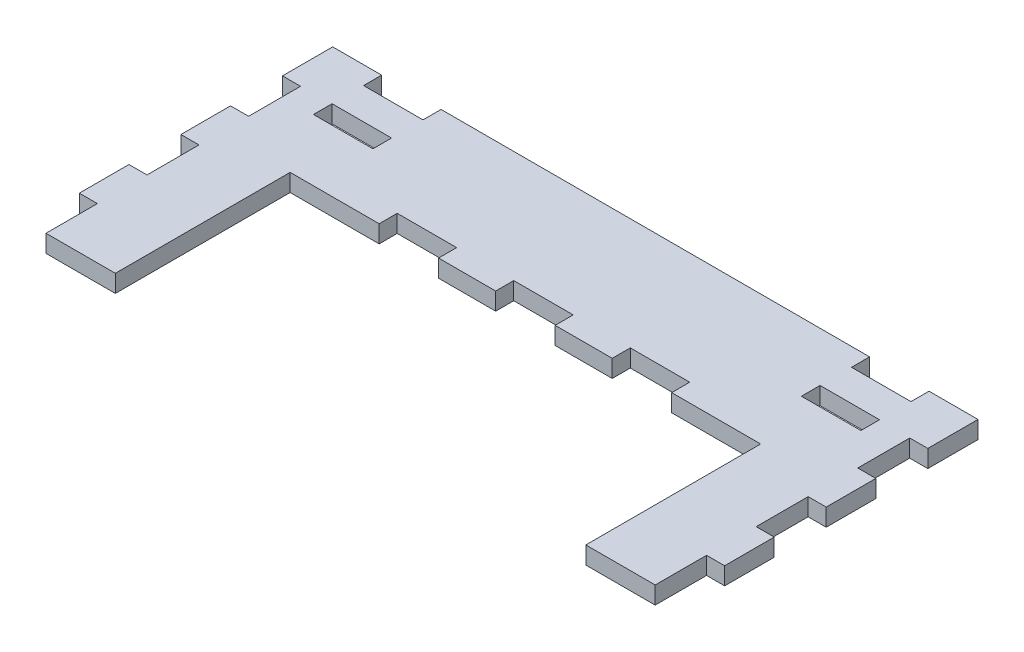
SolidWorks part; units mm, degrees
ref_plane "Front Plane" through (0, 0, 0) normal (0, 0, 1) x (1, 0, 0)
ref_plane "Top Plane" through (0, 0, 0) normal (0, 1, 0) x (1, 0, 0)
ref_plane "Right Plane" through (0, 0, 0) normal (1, 0, 0) x (0, 0, -1)
sketch "Sketch1" plane through (0, 0, 0) normal (0, 1, 0) x (1, 0, 0)
  line L0 (0, 0) -> (0, 52.3) construction
  line L1 (-55.3722, 52.3) -> (55.3722, 52.3)
  line L2 (-55.3722, 52.3) -> (-55.3722, 0)
  line L3 (-55.3722, 0) -> (55.3722, 0) construction
  line L4 (55.3722, 52.3) -> (55.3722, 0)
  line L6 (40.3722, 0) -> (40.3722, 30)
  line L7 (40.3722, 30) -> (-40.3722, 30)
  line L8 (-40.3722, 30) -> (-40.3722, 0)
  line L9 (55.3722, 0) -> (40.3722, 0)
  line L10 (-40.3722, 0) -> (-55.3722, 0)
  dimension "D1" = 15
sketch "Sketch2" plane through (0, 0, 0) normal (1, 0, 0) x (0, 0, -1)
  line L1 (0, 0) -> (52.3, 0)
  line L2 (0, 0) -> (0, 3)
  line L3 (0, 3) -> (52.3, 3)
  line L4 (52.3, 0) -> (52.3, 3)
extrude "Boss-Extrude1" add sketch "Sketch1" along normal up to vertex (3 mm away) up to point (0, 3, -52.3)
sketch "Sketch3" plane through (0, 0, 0) normal (0, 1, 0) x (1, 0, 0)
  line L0 (55.3722, 52.3) -> (55.3722, 0) construction
  line L1 (55.3722, 0) -> (40.3722, 0) construction
  line L2 (40.3722, 0) -> (40.3722, 30) construction
  line L3 (40.3722, 30) -> (-40.3722, 30) construction
  line L4 (-40.3722, 30) -> (-40.3722, 0) construction
  line L5 (-40.3722, 0) -> (-55.3722, 0) construction
  line L6 (-55.3722, 52.3) -> (-55.3722, 0) construction
  line L7 (-55.3722, 52.3) -> (55.3722, 52.3) construction
  line L8 (55.3722, 52.3) -> (55.3722, 0) construction
  line L9 (55.3722, 0) -> (40.3722, 0) construction
  line L10 (40.3722, 0) -> (40.3722, 30) construction
  line L11 (40.3722, 30) -> (-40.3722, 30) construction
  line L12 (-40.3722, 30) -> (-40.3722, 0) construction
  line L13 (-40.3722, 0) -> (-55.3722, 0) construction
  line L14 (-55.3722, 52.3) -> (-55.3722, 0) construction
  line L15 (-55.3722, 52.3) -> (55.3722, 52.3) construction
  line L16 (36.8722, 52.3) -> (36.8722, 30) construction
  line L17 (-36.8722, 52.3) -> (-36.8722, 30) construction
  line L18 (55.3722, 49.3) -> (-55.3722, 49.3) construction
  line L19 (55.3722, 40.7) -> (-55.3722, 40.7) construction
  line L20 (55.3722, 43.7) -> (-55.3722, 43.7) construction
  line L21 (-55.3722, 33) -> (55.3722, 33) construction
  line L22 (52.3722, 52.3) -> (52.3722, 0) construction
  line L23 (-52.3722, 52.3) -> (-52.3722, 0) construction
  line L24 (0, 52.3) -> (0, 0) construction
  line L25 (46.8722, 52.3) -> (46.8722, 49.3) construction
  line L26 (46.8722, 43.7) -> (46.8722, 40.7) construction
  line L27 (40.3722, 30) -> (55.3722, 30) construction
  line L28 (-40.3722, 30) -> (-55.3722, 30) construction
  line L30 (35, 33) -> (35, 30) construction
  line L33 (25, 33) -> (25, 30) construction
  line L34 (25, 31.5) -> (35, 31.5) construction
  line L35 (5, 33) -> (5, 30) construction
  line L36 (5, 31.5) -> (-5, 31.5) construction
  line L37 (25, 31.5) -> (15, 31.5) construction
  line L38 (15, 31.5) -> (5, 31.5) construction
  line L39 (15, 33) -> (15, 30) construction
  line L43 (52.3722, 43.5833) -> (55.3722, 43.5833) construction
  line L44 (55.3722, 34.8667) -> (52.3722, 34.8667) construction
  line L45 (53.8722, 34.8667) -> (53.8722, 43.5833) construction
  line L46 (53.8722, 43.5833) -> (53.8722, 52.3) construction
  line L47 (53.8722, 34.8667) -> (53.8722, 26.15) construction
  line L48 (55.3722, 26.15) -> (52.3722, 26.15) construction
  line L49 (55.3722, 17.4333) -> (52.3722, 17.4333) construction
  line L50 (53.8722, 26.15) -> (53.8722, 17.4333) construction
  line L51 (55.3722, 8.7167) -> (52.3722, 8.7167) construction
  line L52 (53.8722, 17.4333) -> (53.8722, 8.7167) construction
  line L53 (53.8722, 8.7167) -> (53.8722, 0) construction
  dimension "D1" = 10
  dimension "D2" = 8.7167
  dimension "D3" = 10
sketch "Sketch4" plane through (0, 0, 0) normal (0, 1, 0) x (1, 0, 0)
  line L0 (0, 0) -> (0, 52.3) construction
  line L1 (46.9722, 52.4) -> (36.7722, 52.4)
  line L2 (46.9722, 52.4) -> (46.9722, 49.2)
  line L3 (46.9722, 49.2) -> (36.7722, 49.2)
  line L4 (36.7722, 52.4) -> (36.7722, 49.2)
  line L5 (46.9722, 43.8) -> (36.7722, 43.8)
  line L6 (46.9722, 43.8) -> (46.9722, 40.6)
  line L7 (46.9722, 40.6) -> (36.7722, 40.6)
  line L8 (36.7722, 43.8) -> (36.7722, 40.6)
  line L9 (55.4722, 43.6833) -> (52.2722, 43.6833)
  line L10 (55.4722, 43.6833) -> (55.4722, 34.7667)
  line L11 (55.4722, 34.7667) -> (52.2722, 34.7667)
  line L12 (52.2722, 43.6833) -> (52.2722, 34.7667)
  line L13 (55.4722, 26.25) -> (52.2722, 26.25)
  line L14 (55.4722, 26.25) -> (55.4722, 17.3333)
  line L15 (55.4722, 17.3333) -> (52.2722, 17.3333)
  line L16 (52.2722, 26.25) -> (52.2722, 17.3333)
  line L17 (55.4722, 8.8167) -> (52.2722, 8.8167)
  line L18 (55.4722, 8.8167) -> (55.4722, -0.1)
  line L19 (55.4722, -0.1) -> (52.2722, -0.1)
  line L20 (52.2722, 8.8167) -> (52.2722, -0.1)
  line L21 (20, 33.1) -> (20, 33) construction
  line L22 (20, 29.9) -> (20, 30) construction
  line L23 (40.3722, 30) -> (-40.3722, 30) construction
  line L24 (-55.3722, 33) -> (55.3722, 33) construction
  line L25 (25.1, 33.1) -> (14.9, 33.1)
  line L26 (25.1, 33.1) -> (25.1, 29.9)
  line L27 (25.1, 29.9) -> (14.9, 29.9)
  line L28 (14.9, 33.1) -> (14.9, 29.9)
  line L29 (5.1, 33.1) -> (-5.1, 33.1)
  line L30 (5.1, 33.1) -> (5.1, 29.9)
  line L31 (5.1, 29.9) -> (-5.1, 29.9)
  line L32 (-5.1, 33.1) -> (-5.1, 29.9)
  line L33 (0, 0) -> (0, 52.3) construction
  line L34 (41.8722, 52.4) -> (41.8722, 52.3) construction
  line L35 (41.8722, 49.2) -> (41.8722, 49.3) construction
  line L36 (36.7722, 50.8) -> (36.8722, 50.8) construction
  line L37 (46.9722, 50.8) -> (46.8722, 50.8) construction
  line L38 (46.8722, 52.3) -> (46.8722, 49.3) construction
  line L39 (-55.3722, 52.3) -> (55.3722, 52.3) construction
  line L40 (55.3722, 49.3) -> (-55.3722, 49.3) construction
  line L41 (36.8722, 52.3) -> (36.8722, 30) construction
  line L42 (52.2722, 39.225) -> (52.3722, 39.225) construction
  line L43 (55.4722, 39.225) -> (55.3722, 39.225) construction
  line L44 (53.8722, 43.6833) -> (53.8722, 43.5833) construction
  line L45 (53.8722, 34.7667) -> (53.8722, 34.8667) construction
  line L46 (53.8722, 26.25) -> (53.8722, 26.15) construction
  line L47 (53.8722, 17.3333) -> (53.8722, 17.4333) construction
  line L48 (53.8722, 8.8167) -> (53.8722, 8.7167) construction
  line L49 (53.8722, -0.1) -> (53.8722, 0) construction
  line L50 (41.8722, 43.8) -> (41.8722, 43.7) construction
  line L51 (41.8722, 40.6) -> (41.8722, 40.7) construction
  line L52 (55.3722, 43.7) -> (-55.3722, 43.7) construction
  line L53 (55.3722, 40.7) -> (-55.3722, 40.7) construction
  line L54 (52.3722, 43.5833) -> (55.3722, 43.5833) construction
  line L55 (55.3722, 34.8667) -> (52.3722, 34.8667) construction
  line L56 (52.3722, 52.3) -> (52.3722, 0) construction
  line L57 (55.3722, 52.3) -> (55.3722, 0) construction
  line L58 (55.3722, 26.15) -> (52.3722, 26.15) construction
  line L59 (55.3722, 17.4333) -> (52.3722, 17.4333) construction
  line L60 (55.3722, 0) -> (40.3722, 0) construction
  line L61 (55.3722, 8.7167) -> (52.3722, 8.7167) construction
  line L70 (25.1, 31.5) -> (25, 31.5) construction
  line L71 (14.9, 31.5) -> (15, 31.5) construction
  line L72 (5.1, 31.5) -> (5, 31.5) construction
  line L73 (5, 33) -> (5, 30) construction
  line L74 (15, 33) -> (15, 30) construction
  line L75 (25, 33) -> (25, 30) construction
  line L76 (-55.4722, 8.8167) -> (-52.2722, 8.8167)
  line L77 (-55.4722, 8.8167) -> (-55.4722, -0.1)
  line L78 (-55.4722, -0.1) -> (-52.2722, -0.1)
  line L79 (-52.2722, 8.8167) -> (-52.2722, -0.1)
  line L80 (-55.4722, 26.25) -> (-52.2722, 26.25)
  line L81 (-55.4722, 26.25) -> (-55.4722, 17.3333)
  line L82 (-55.4722, 17.3333) -> (-52.2722, 17.3333)
  line L83 (-52.2722, 26.25) -> (-52.2722, 17.3333)
  line L84 (-55.4722, 43.6833) -> (-52.2722, 43.6833)
  line L85 (-55.4722, 43.6833) -> (-55.4722, 34.7667)
  line L86 (-55.4722, 34.7667) -> (-52.2722, 34.7667)
  line L87 (-52.2722, 43.6833) -> (-52.2722, 34.7667)
  line L88 (-46.9722, 52.4) -> (-46.9722, 49.2)
  line L89 (-46.9722, 52.4) -> (-36.7722, 52.4)
  line L90 (-36.7722, 52.4) -> (-36.7722, 49.2)
  line L91 (-46.9722, 49.2) -> (-36.7722, 49.2)
  line L92 (-46.9722, 43.8) -> (-46.9722, 40.6)
  line L93 (-46.9722, 40.6) -> (-36.7722, 40.6)
  line L94 (-36.7722, 43.8) -> (-36.7722, 40.6)
  line L95 (-46.9722, 43.8) -> (-36.7722, 43.8)
  line L100 (-25.1, 33.1) -> (-25.1, 29.9)
  line L101 (-25.1, 29.9) -> (-14.9, 29.9)
  line L102 (-14.9, 33.1) -> (-14.9, 29.9)
  line L103 (-25.1, 33.1) -> (-14.9, 33.1)
  dimension "D1" = 0.1
extrude "Cut-Extrude1" cut sketch "Sketch4" along normal through all
